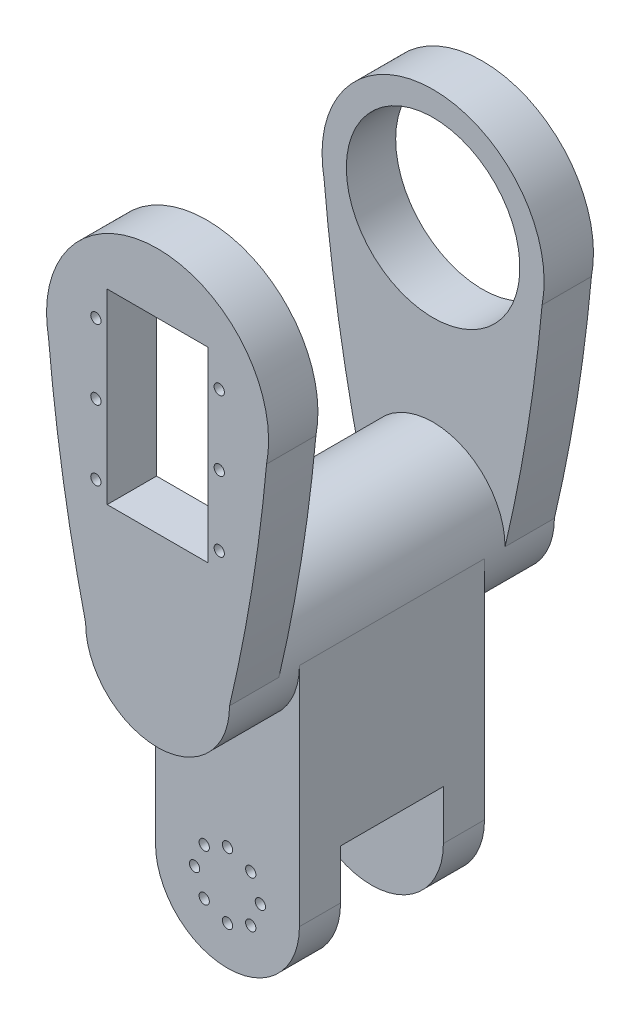
SolidWorks part; units mm, degrees
ref_plane "Front Plane" through (0, 0, 0) normal (0, 0, 1) x (1, 0, 0)
ref_plane "Top Plane" through (0, 0, 0) normal (0, 1, 0) x (1, 0, 0)
ref_plane "Right Plane" through (0, 0, 0) normal (1, 0, 0) x (0, 0, -1)
sketch "Sketch2" plane through (0, 0, 0) normal (0, 0, 1) x (1, 0, 0)
  line L0 (-17.5, -27.5) -> (17.5, -27.5)
  line L1 (17.5, -27.5) -> (-17.5, -27.5)
  line L2 (17.5, -27.5) -> (17.5, 27.5)
  line L3 (17.5, 27.5) -> (-17.5, 27.5)
  line L4 (-17.5, -27.5) -> (-17.5, 27.5)
  line L5 (0, 27.5) -> (0, -27.5) construction
  line L6 (17.5, 0) -> (-17.5, 0) construction
  arc A0 (17.5, -27.5) -> (-17.5, -27.5) centre (0, -27.5) cw
  arc A1 (-17.5, 27.5) -> (17.5, 27.5) centre (0, 27.5) cw
  point P0 (0, 0)
  dimension "D1" = 55
  dimension "D2" = 35
extrude "Boss-Extrude1" add sketch "Sketch2" along normal blind 45 contours A1 L3 | L4 L0 L2 L3 | A0 L0 region at (0, 0, 0) region at (0, -34.9272, 0) region at (0, 34.9272, 0)
sketch "Sketch5" plane through (0, 0, 45) normal (0, 0, 1) x (1, 0, 0)
  arc A0 (17.5, 27.5) -> (-17.5, 27.5) centre (0, 27.5) ccw
  arc A1 (-17.5, 27.5) -> (17.5, 27.5) centre (0, 27.5) ccw
extrude "Boss-Extrude2" add sketch "Sketch5" along normal blind 5
sketch "Sketch6" plane through (0, 0, 50) normal (0, 0, 1) x (1, 0, 0)
  line L0 (17.5, 67.5) -> (17.5, 27.5)
  line L1 (-17.5, 27.5) -> (-17.5, 67.5)
  line L2 (-17.5, 67.5) -> (17.5, 67.5)
  arc A0 (17.5, 27.5) -> (-17.5, 27.5) centre (0, 27.5) cw
  arc A1 (17.5, 67.5) -> (-17.5, 67.5) centre (0, 67.5) ccw
  circle M2 centre (0, 27.5) radius 17.5
  dimension "50" = 40
extrude "Boss-Extrude3" add sketch "Sketch6" along normal blind 12 contours L2 A1 | L2 L1 L0 M2 | M2 region at (0, 54.0817, 50) region at (0, 74.9272, 50) region at (0, 27.5, 50)
sketch "Sketch7" plane through (0, 0, 0) normal (0, 0, -1) x (-1, 0, 0)
  arc A0 (17.5, 27.5) -> (-17.5, 27.5) centre (0, 27.5) cw
  arc A1 (-17.5, 27.5) -> (17.5, 27.5) centre (0, 27.5) cw
extrude "Boss-Extrude4" add sketch "Sketch7" along normal blind 5
sketch "Sketch8" plane through (0, 0, -5) normal (0, 0, -1) x (-1, 0, 0)
  line L0 (17.5, 27.5) -> (17.5, 67.5)
  line L1 (17.5, 67.5) -> (-17.5, 67.5)
  line L2 (-17.5, 67.5) -> (-17.5, 27.5)
  arc A0 (-17.5, 27.5) -> (17.5, 27.5) centre (0, 27.5) ccw
  arc A1 (17.5, 67.5) -> (-17.5, 67.5) centre (0, 67.5) ccw
  circle M5 centre (0, 27.5) radius 17.5
extrude "Boss-Extrude5" add sketch "Sketch8" along normal blind 12 contours L1 A1 | L1 L2 L0 M5 | M5 region at (0, 54.0817, -5) region at (0, 27.5, -5) region at (0, 74.9272, -5)
sketch "Sketch11" plane through (0, 0, 62) normal (0, 0, 1) x (1, 0, 0)
  line L2 (-17.5, 67.5) -> (-17.5, 27.5)
  line L3 (17.5, 27.5) -> (17.5, 67.5)
  line L4 (-17.5, 67.5) -> (-17.5, 27.5)
  line L5 (17.5, 27.5) -> (17.5, 67.5)
  arc A0 (-17.5, 67.5) -> (17.5, 67.5) centre (0, 88.0609) cw
  arc A3 (17.5, 67.5) -> (-17.5, 67.5) centre (0, 67.5) ccw
  arc A4 (-17.5, 27.5) -> (17.5, 27.5) centre (0, 27.5) ccw
  arc A6 (-17.5, 27.5) -> (17.5, 27.5) centre (0, 27.5) ccw
  dimension "D2" = 27
  dimension "D1" = 0
extrude "Boss-Extrude6" add sketch "Sketch11" against normal blind 12
sketch "Sketch12" plane through (0, 0, -17) normal (0, 0, -1) x (-1, 0, 0)
  line L2 (-17.5, 67.5) -> (-17.5, 27.5)
  line L3 (17.5, 27.5) -> (17.5, 67.5)
  arc A1 (17.5, 67.5) -> (-17.5, 67.5) centre (0, 88.0609) ccw
  arc A3 (17.5, 67.5) -> (-17.5, 67.5) centre (0, 67.5) ccw
  arc A4 (-17.5, 27.5) -> (17.5, 27.5) centre (0, 27.5) ccw
  arc A5 (17.5, 67.5) -> (-17.5, 67.5) centre (0, 67.5) ccw
  dimension "D2" = 27
  dimension "D1" = 0
extrude "Boss-Extrude7" add sketch "Sketch12" against normal blind 12
sketch "Sketch14" plane through (0, 0, 62) normal (0, 0, 1) x (1, 0, 0)
  line L1 (-12.25, 100.4109) -> (12.25, 100.4109)
  line L2 (-12.25, 100.4109) -> (-12.25, 55.0109)
  line L3 (-12.25, 55.0109) -> (12.25, 55.0109)
  line L4 (12.25, 100.4109) -> (12.25, 55.0109)
  line L5 (0, 55.0109) -> (0, 100.4109) construction
  line L6 (-12.25, 77.7109) -> (12.25, 77.7109) construction
  point P0 (0, 77.7109)
  point P4 (0, 88.0609)
  dimension "D1" = 24.5
  dimension "D4" = 45.4
  dimension "12,35" = 12.35
extrude "Cut-Extrude3" cut sketch "Sketch14" against normal blind 12
sketch "Sketch15" plane through (0, 0, -17) normal (0, 0, -1) x (-1, 0, 0)
  circle A0 centre (0, 88.0609) radius 21.1
  dimension "D1" = 42.2
extrude "Cut-Extrude4" cut sketch "Sketch15" against normal blind 12
sketch "Sketch17" plane through (-17.5, 0, 0) normal (-1, 0, 0) x (0, 0, 1)
  line L0 (22.5, -27.5) -> (35, -27.5)
  line L1 (45, -27.5) -> (0, -27.5) construction
  line L2 (22.5, -27.5) -> (10, -27.5)
  line L3 (10, -27.5) -> (10, -45)
  line L4 (0, -45) -> (45, -45) construction
  line L5 (10, -45) -> (35, -45)
  line L6 (35, -45) -> (35, -27.5)
  line L7 (35, -27.5) -> (34.9842, -25.1645)
  line L8 (35, -27.5) -> (35, -15.5)
  line L9 (10, -27.5) -> (10, -15.5)
  line L10 (10, -15.5) -> (35, -15.5)
  line M4 (0, -27.5) -> (45, -27.5)
  dimension "D1" = 12.5
  dimension "12,5" = 12.5
  dimension "D2" = 12
extrude "Cut-Extrude5" cut sketch "Sketch17" against normal through all contours L5 L6 L3 M4 | L10 L9 L8 M4 region at (-17.5, -21.5, 22.5) region at (-17.5, -36.25, 22.5)
sketch "Sketch21" plane through (0, 0, 45) normal (0, 0, 1) x (1, 0, 0)
  circle A9 centre (8, -27.5) radius 1.25
  circle A10 centre (5.6569, -33.1569) radius 1.25
  circle A11 centre (0, -35.5) radius 1.25
  circle A12 centre (-5.6569, -33.1569) radius 1.25
  circle A13 centre (-8, -27.5) radius 1.25
  circle A14 centre (-5.6569, -21.8431) radius 1.25
  circle A15 centre (0, -19.5) radius 1.25
  circle A16 centre (5.6569, -21.8431) radius 1.25
  point P0 (0, -27.5)
  point P3 (0, -32.5)
  point P21 (0, -32.5)
  point P24 (0, -27.5)
  dimension "D1" = 2.5
  dimension "D2" = 8
  dimension "D3" = 8
extrude "Cut-Extrude7" cut sketch "Sketch21" against normal blind 12
sketch "Sketch23" plane through (0, 0, 0) normal (0, 0, -1) x (-1, 0, 0)
  circle A0 centre (0, -27.5) radius 10.1
  dimension "D1" = 20.2
extrude "Boss-Extrude8" add sketch "Sketch23" along normal blind 6
sketch "Sketch24" plane through (0, 0, -6) normal (0, 0, -1) x (-1, 0, 0)
  circle A0 centre (0, -27.5) radius 8.5
  dimension "D1" = 17
extrude "Cut-Extrude8" cut sketch "Sketch24" against normal blind 6
sketch "Sketch25" plane through (0, 0, 0) normal (0, 0, -1) x (-1, 0, 0)
  circle A0 centre (0, -27.5) radius 2.7
  dimension "D1" = 5.4
extrude "Cut-Extrude9" cut sketch "Sketch25" against normal blind 18
sketch "Sketch26" plane through (0, 0, 62) normal (0, 0, 1) x (1, 0, 0)
  arc A0 (26.9918, 88.7245) -> (17.5, 27.5) centre (-371.8448, 119.2095) cw
  arc A3 (17.5, 67.5) -> (-17.5, 67.5) centre (0, 88.0609) ccw construction
  arc A4 (-26.9918, 88.7245) -> (-17.5, 27.5) centre (371.8448, 119.2095) ccw
  line M5 (17.5, 27.5) -> (17.5, 67.5)
  arc M6 (17.5, 67.5) -> (-17.5, 67.5) centre (0, 88.0609) ccw
  line M7 (-17.5, 67.5) -> (-17.5, 27.5)
extrude "Boss-Extrude9" add sketch "Sketch26" against normal blind 12 contours A4 M6 M7 | A0 M6 M5 region at (-20.6675, 57.1072, 62) region at (20.6675, 57.1072, 62)
sketch "Sketch30" plane through (0, 0, 62) normal (0, 0, 1) x (1, 0, 0)
  line L0 (12.25, 100.4109) -> (-12.25, 100.4109) construction
  line L1 (12.25, 55.0109) -> (12.25, 100.4109) construction
  line L2 (0, 100.4109) -> (0, 88.0609)
  circle A0 centre (15, 92.9109) radius 1.25
  circle A1 centre (15, 75.9109) radius 1.25
  circle A2 centre (15, 58.9109) radius 1.25
  circle A3 centre (-15, 92.9109) radius 1.25
  circle A4 centre (-15, 75.9109) radius 1.25
  circle A5 centre (-15, 58.9109) radius 1.25
  point P8 (15, 58.9109)
  dimension "D2" = 2.5
  dimension "D1" = 2.75
  dimension "7,5" = 7.5
  dimension "D3" = 3
extrude "Cut-Extrude11" cut sketch "Sketch30" against normal blind 12 contours A0 | A3 | A4 | A1 | A2 | A5
sketch "Sketch31" plane through (0, 0, 50) normal (0, 0, -1) x (-1, 0, 0)
  line L0 (0, 100.4109) -> (0, 89.0564)
  line L1 (-12.25, 100.4109) -> (12.25, 100.4109) construction
  circle A0 centre (15, 92.9109) radius 2
  circle A1 centre (15, 75.9109) radius 2
  circle A2 centre (15, 58.9109) radius 2
  circle A3 centre (-15, 58.9109) radius 2
  circle A4 centre (-15, 75.9109) radius 2
  circle A5 centre (-15, 92.9109) radius 2
  dimension "D1" = 4
  dimension "D2" = 3
extrude "Cut-Extrude12" cut sketch "Sketch31" against normal blind 2.5 contours A0 | A1 | A2 | A3 | A4 | A5
sketch "Sketch32" plane through (0, 0, -17) normal (0, 0, -1) x (-1, 0, 0)
  arc A0 (26.9918, 88.7245) -> (17.5, 27.5) centre (-371.8448, 119.2095) cw
  arc A1 (17.5, 67.5) -> (-17.5, 67.5) centre (0, 88.0609) ccw construction
  arc A2 (-26.9918, 88.7245) -> (-17.5, 27.5) centre (371.8448, 119.2095) ccw
  line M2 (17.5, 27.5) -> (17.5, 67.5)
  arc M3 (17.5, 67.5) -> (-17.5, 67.5) centre (0, 88.0609) ccw
  line M4 (-17.5, 67.5) -> (-17.5, 27.5)
extrude "Boss-Extrude11" add sketch "Sketch32" against normal blind 12 contours A2 M3 M4 | A0 M3 M2 region at (20.6675, 57.1072, -17) region at (-20.6675, 57.1072, -17)
